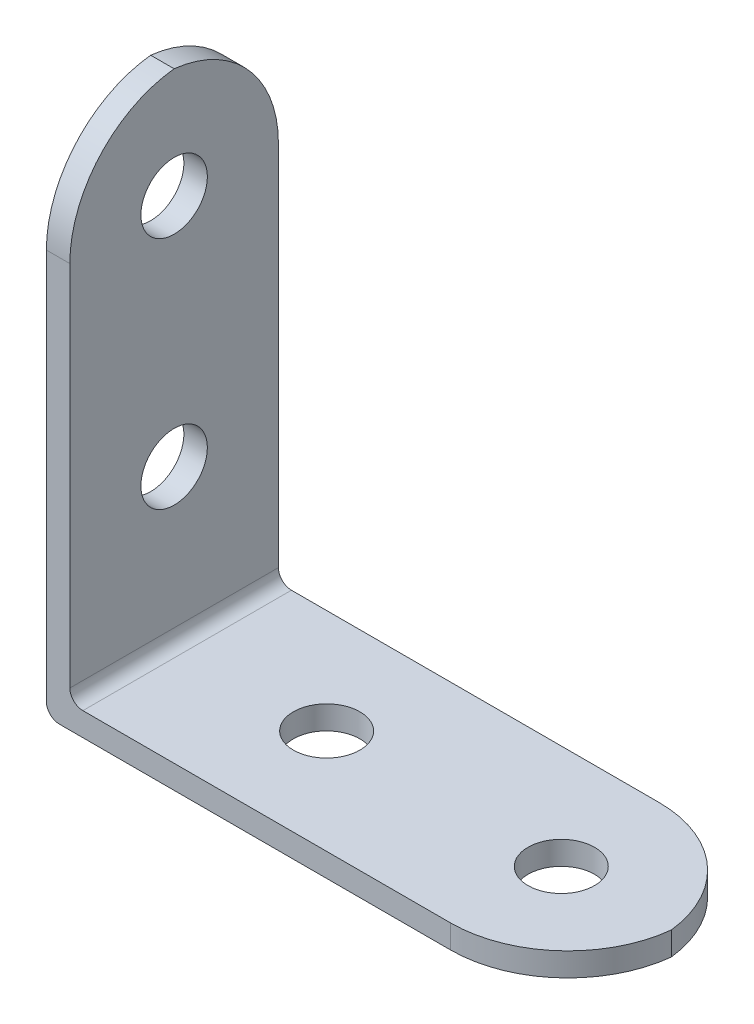
SolidWorks part; units mm, degrees
ref_plane "Alzado" through (0, 0, 0) normal (0, 0, 1) x (1, 0, 0)
ref_plane "Planta" through (0, 0, 0) normal (0, 1, 0) x (1, 0, 0)
ref_plane "Vista lateral" through (0, 0, 0) normal (1, 0, 0) x (0, 0, -1)
sketch "Croquis1" plane through (0, 0, 0) normal (1, 0, 0) x (0, 0, -1)
  line L0 (-8, 40) -> (-8, 0) construction
  line L1 (0, 0) -> (-16, 0)
  line L2 (0, 0) -> (0, 40)
  line L3 (0, 40) -> (-16, 40)
  line L4 (-16, 0) -> (-16, 40)
  circle A0 centre (-8, 31.5) radius 2.55
  circle A1 centre (-8, 13.5) radius 2.55
  dimension "D3" = 8.5
  dimension "D4" = 18
  dimension "D5" = 5.1
  dimension "D1" = 16
  dimension "D2" = 40
extrude "Saliente-Extruir1" add sketch "Croquis1" along normal blind 1.8
sketch "Croquis2" plane through (1.8, 0, 0) normal (1, 0, 0) x (0, 0, -1)
  line L0 (0, 0) -> (0, 40) construction
  line L1 (-16, 0) -> (0, 0)
  line L2 (-16, 0) -> (-16, 1.8)
  line L3 (-16, 1.8) -> (0, 1.8)
  line L4 (0, 0) -> (0, 1.8)
  dimension "D1" = 1.8
extrude "Saliente-Extruir2" add sketch "Croquis2" along normal blind 38.2
sketch "Croquis3" plane through (0, 1.8, 0) normal (0, 1, 0) x (1, 0, 0)
  line L0 (40, -8) -> (1.8, -8) construction
  line L1 (40, 0) -> (40, -16) construction
  line L2 (1.8, 0) -> (1.8, -16) construction
  circle A0 centre (31.5, -8) radius 2.55
  circle A1 centre (13.5, -8) radius 2.55
  dimension "D1" = 5.1
  dimension "D2" = 8.5
  dimension "D3" = 18
extrude "Cortar-Extruir1" cut sketch "Croquis3" against normal blind 38.2
fillet "Redondeo1" radius 1 1 edges at (1.8, 1.8, 8)
fillet "Redondeo2" radius 9 4 edges at (40, 0.9, 16) (40, 0.9, 0) (0.9, 40, 0) (0.9, 40, 16)
fillet "Redondeo3" radius 1 1 edges at (0, 0, 8)
